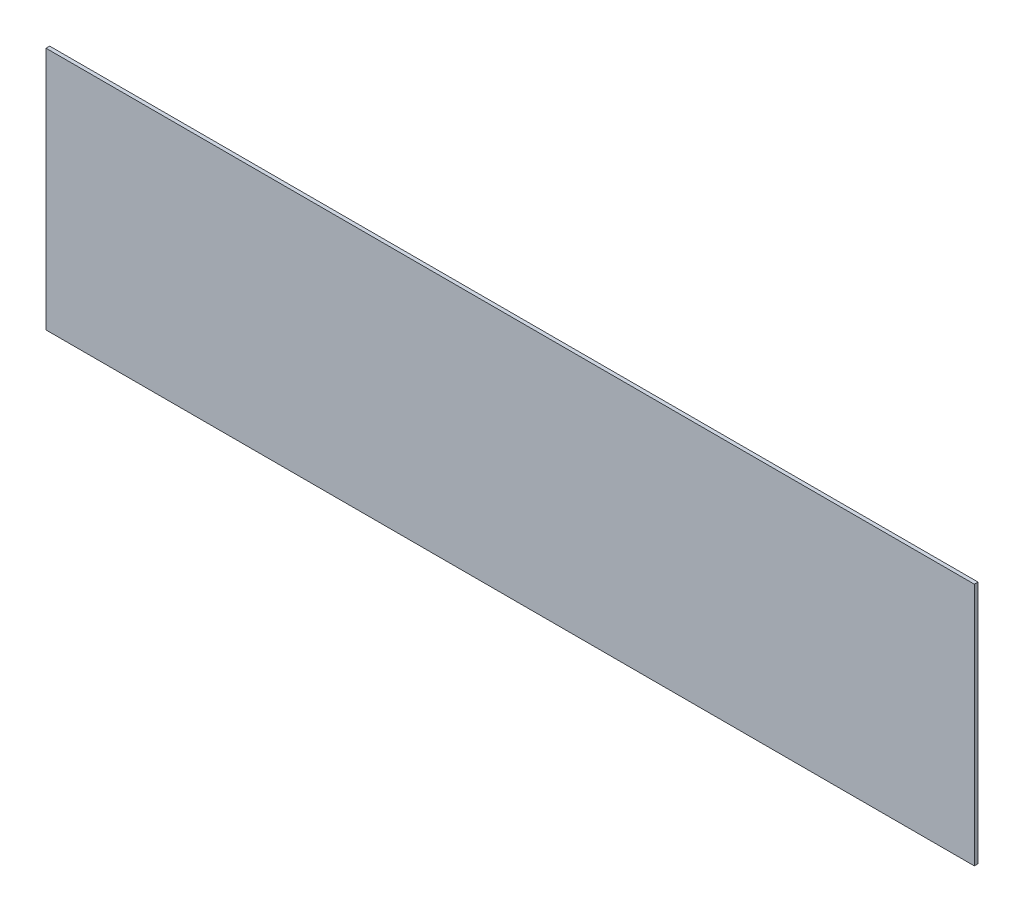
SolidWorks part; units mm, degrees
material "Pine"
ref_plane "Front Plane" through (0, 0, 0) normal (0, 0, 1) x (1, 0, 0)
ref_plane "Top Plane" through (0, 0, 0) normal (0, 1, 0) x (1, 0, 0)
ref_plane "Right Plane" through (0, 0, 0) normal (1, 0, 0) x (0, 0, -1)
sketch "Sketch1" plane through (0, 0, 0) normal (0, 0, 1) x (1, 0, 0)
  line L1 (-800.1, 210.312) -> (0, 210.312)
  line L2 (-800.1, 210.312) -> (-800.1, 0)
  line L3 (-800.1, 0) -> (0, 0)
  line L4 (0, 210.312) -> (0, 0)
  dimension "D1" = 800.1
  dimension "D2" = 210.312
extrude "Boss-Extrude1" add sketch "Sketch1" along normal blind 3.175
